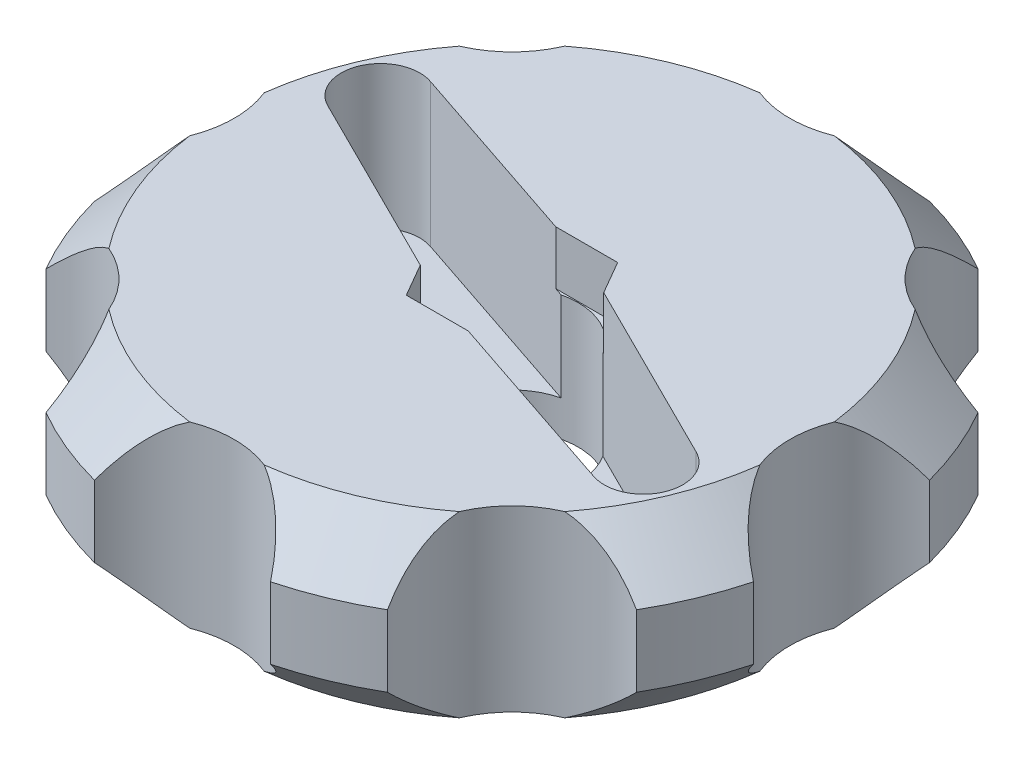
SolidWorks part; units mm, degrees
ref_plane "Front Plane" through (0, 0, 0) normal (0, 0, 1) x (1, 0, 0)
ref_plane "Top Plane" through (0, 0, 0) normal (0, 1, 0) x (1, 0, 0)
ref_plane "Right Plane" through (0, 0, 0) normal (1, 0, 0) x (0, 0, -1)
sketch "Sketch1" plane through (0, 0, 0) normal (0, 1, 0) x (1, 0, 0)
  line L0 (0, -21.2055) -> (21.2055, -21.2055) construction
  line L1 (0, -21.2055) -> (14.9946, -14.9946) construction
  line L2 (14.9946, -14.9946) -> (21.2055, 0) construction
  line L3 (21.2055, 0) -> (14.9946, 14.9946) construction
  line L4 (14.9946, 14.9946) -> (0, 21.2055) construction
  line L5 (0, 21.2055) -> (-14.9946, 14.9946) construction
  line L6 (-14.9946, 14.9946) -> (-21.2055, 0) construction
  line L7 (-21.2055, 0) -> (-14.9946, -14.9946) construction
  line L8 (-14.9946, -14.9946) -> (0, -21.2055) construction
  line L9 (21.2055, -21.2055) -> (21.2055, 0) construction
  arc A1 (4.9292, -18.444) -> (-4.9292, -18.444) centre (0, -21.2055) ccw
  arc A2 (-9.5565, -16.5274) -> (-16.5274, -9.5565) centre (-14.9946, -14.9946) ccw
  arc A3 (-18.444, -4.9292) -> (-18.444, 4.9292) centre (-21.2055, 0) ccw
  arc A4 (-16.5274, 9.5565) -> (-9.5565, 16.5274) centre (-14.9946, 14.9946) ccw
  arc A5 (-4.9292, 18.444) -> (4.9292, 18.444) centre (0, 21.2055) ccw
  arc A6 (9.5565, 16.5274) -> (16.5274, 9.5565) centre (14.9946, 14.9946) ccw
  arc A7 (-9.5565, -16.5274) -> (-4.9292, -18.444) centre (0, 0) ccw
  arc A8 (-16.5274, -9.5565) -> (-18.444, -4.9292) centre (0, 0) cw
  arc A9 (-18.444, 4.9292) -> (-16.5274, 9.5565) centre (0, 0) cw
  arc A10 (-9.5565, 16.5274) -> (-4.9292, 18.444) centre (0, 0) cw
  arc A11 (4.9292, 18.444) -> (9.5565, 16.5274) centre (0, 0) cw
  arc A13 (18.444, 4.9292) -> (18.444, -4.9292) centre (21.2055, 0) ccw
  arc A14 (16.5274, -9.5565) -> (9.5565, -16.5274) centre (14.9946, -14.9946) ccw
  arc A15 (4.9292, -18.444) -> (9.5565, -16.5274) centre (0, 0) ccw
  arc A16 (16.5274, -9.5565) -> (18.444, -4.9292) centre (0, 0) ccw
  arc A17 (18.444, 4.9292) -> (16.5274, 9.5565) centre (0, 0) ccw
  circle A18 centre (0, 0) radius 19.5913 construction
  point P23 (0, 0)
  point P27 (-4.9292, -18.444)
  point P29 (-4.9292, -18.444)
  point P31 (-7.3059, -17.6381)
  point P33 (-7.4973, -18.1)
  point P37 (-9.5565, -16.5274)
  dimension "D1" = 16.23
  dimension "D2" = 0.5
  dimension "D3" = 5.65
  dimension "D4" = 8
extrude "Boss-Extrude1" add sketch "Sketch1" along normal blind 10
chamfer "Chamfer1" distance 3 angle 45 16 edges at (-7.3059, 0, -17.6381) (7.3059, 0, -17.6381) (17.6381, 0, -7.3059) (17.6381, 0, 7.3059) (7.3059, 0, 17.6381) (-7.3059, 0, 17.6381) (-17.6381, 0, 7.3059) (-17.6381, 0, -7.3059) (-17.6381, 10, -7.3059) (-7.3059, 10, -17.6381) (7.3059, 10, -17.6381) (17.6381, 10, -7.3059) (17.6381, 10, 7.3059) (7.3059, 10, 17.6381) (-7.3059, 10, 17.6381) (-17.6381, 10, 7.3059)
sketch "Sketch2" plane through (0, 10, 0) normal (0, 1, 0) x (1, 0, 0)
  point P0 (0, 0)
hole_wizard "M4 Clearance Hole1" positions "Sketch2" profile "Sketch3" hole size "M4" standard "ANSI Metric" end condition through all
sketch "Sketch3" plane through (0, 10, 0) normal (1, 0, 0) x (0, 0, 1)
  line L0 (0, 0) -> (0, 10)
  line L1 (0, 10) -> (2.4, 10)
  line L2 (2.4, 10) -> (2.4, 0)
  line L5 (2.4, 0) -> (0, 0)
  line L11 (0, -6.35) -> (0, 107.95) construction
  dimension "Thru Hole Dia." = 4.8
  dimension "Thru Hole Depth" = 10
sketch "Sketch4" plane through (0, 10, 0) normal (0, 1, 0) x (1, 0, 0)
  line L0 (14.3201, -5.9316) -> (-14.3201, 5.9316) construction
  line L1 (-14.8665, 6.1579) -> (-14.3201, 5.9316) construction
  line L2 (-13.5456, 3.2352) -> (-3.1488, -1.9429)
  line L3 (-11.8658, 7.2905) -> (-0.8527, 3.6004)
  line L4 (1.4159, 3.4184) -> (-1.4159, -3.4184) construction
  line L5 (13.5456, -3.2352) -> (3.1488, 1.9429)
  line L6 (11.8658, -7.2905) -> (0.8527, -3.6004)
  arc A0 (-12.7583, 9.806) -> (-15.9553, 2.0876) centre (0, 0) ccw construction
  arc A1 (-13.5456, 3.2352) -> (-11.8658, 7.2905) centre (-12.5648, 5.2045) cw
  circle A2 centre (0, 0) radius 3.7
  arc A3 (11.8658, -7.2905) -> (13.5456, -3.2352) centre (12.5648, -5.2045) ccw
  point P5 (0, 0)
  point P18 (-14.5973, 6.0464)
  point P27 (0, 0)
  circle M3 centre (0, 0) radius 2.4
  dimension "D2" = 7.4
  dimension "D5" = 2.2
  dimension "D1" = 31
  dimension "D3" = 0.3
  dimension "D4" = 6
extrude "Cut-Extrude1" cut sketch "Sketch4" against normal offset from surface (8 mm away) 2 contours A2 L3 A1 L2 | A2 M3 | M3 | L6 A3 L5 A2 region at (-8.2889, 10, -3.4334) region at (-3.3217, 10, -1.3759) region at (8.2889, 10, 3.4334) region at (0, 10, 0) up to face at (0, 0, 2.4)
extrude "Cut-Extrude2" cut sketch "Sketch4<3>" against normal through all contours A2 M3 | M3 region at (-3.3217, 10, -1.3759) region at (0, 10, 0)
sketch "Sketch4<3>" plane through (0, 10, 0) normal (0, 1, 0) x (1, 0, 0) same geometry as "Sketch4"
sketch "Sketch5" plane through (0, 10, 0) normal (0, 1, 0) x (1, 0, 0)
  line L1 (2.1651, -3.75) -> (4.3301, 0)
  line L2 (4.3301, 0) -> (2.1651, 3.75)
  line L3 (2.1651, 3.75) -> (-2.1651, 3.75)
  line L4 (-2.1651, 3.75) -> (-4.3301, 0)
  line L5 (-4.3301, 0) -> (-2.1651, -3.75)
  line L6 (-2.1651, -3.75) -> (2.1651, -3.75)
  circle A0 centre (0, 0) radius 3.75 construction
  dimension "D1" = 7.5
extrude "Cut-Extrude3" cut sketch "Sketch5" against normal blind 3
